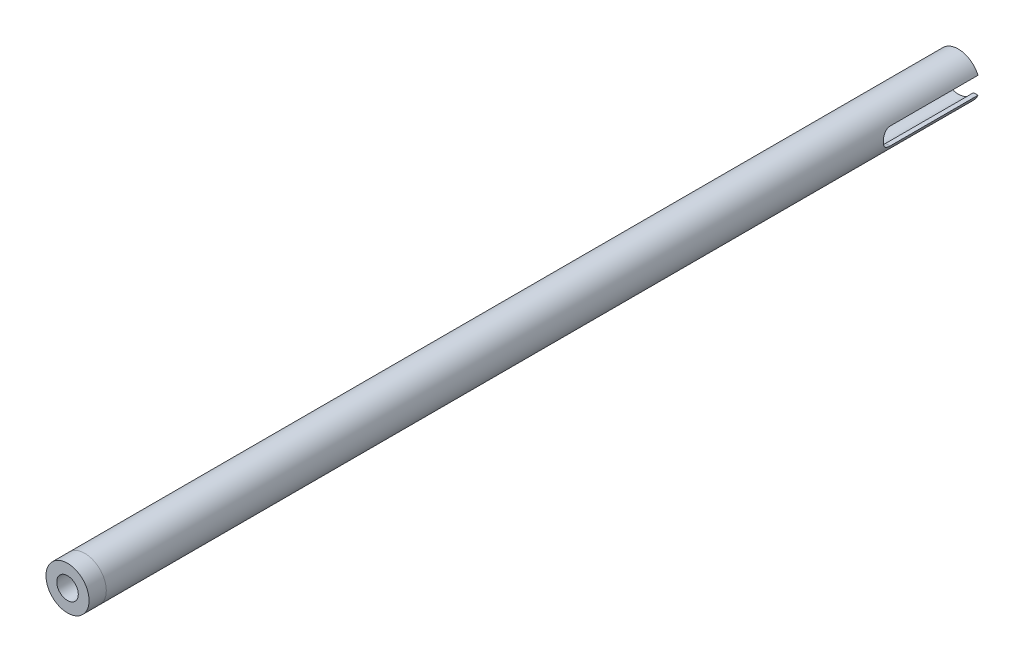
SolidWorks part; units mm, degrees
material "AISI 4130 Steel, annealed at 865C"
ref_plane "Front Plane" through (0, 0, 0) normal (0, 0, 1) x (1, 0, 0)
ref_plane "Top Plane" through (0, 0, 0) normal (0, 1, 0) x (1, 0, 0)
ref_plane "Right Plane" through (0, 0, 0) normal (1, 0, 0) x (0, 0, -1)
sketch "Axis" plane through (0, 0, 0) normal (0, 1, 0) x (1, 0, 0)
  line L0 (0, 0) -> (0, 328.0702) construction
  line L1 (0, 0) -> (0, -28.575) construction
  line L2 (0, 328.0702) -> (-7.9375, 328.0702) construction
  line L4 (0, 356.4735) -> (-26.4371, 261.8721) construction
  dimension "D1" = 28.575
  dimension "D2" = 7.9375
sketch "Sketch1" plane through (0, 0, 0) normal (0, 0, 1) x (1, 0, 0)
  line L0 (-7.9375, 0) -> (7.9375, 0) construction
  line L1 (-7.2748, 3.175) -> (7.2748, 3.175)
  line L2 (-7.2748, -3.175) -> (7.2748, -3.175)
  circle A0 centre (0, 0) radius 7.9375
  circle A1 centre (0, 0) radius 6.4643
  circle A2 centre (0, 0) radius 3.9688
  dimension "D1" = 15.875
  dimension "D3" = 7.9375
  dimension "D2" = 1.4732
  dimension "D4" = 6.35
extrude "Threaded insert 1-1" add sketch "Sketch1" against normal blind 6.35 contours A2 L1 A1 | A1 L1 A0 | A2 L0 A1 L1 | A1 L0 A0 L1 | L0 A1 L2 A0 | L0 A2 L2 A1 | A2 L2 A1 | A1 L2 A0 | L0 A1 L2 A2 | L0 A0 L2 A1 | A0 L0 A1 L1 | A1 L0 A2 L1 region at (4.8156, 1.6537, 0) region at (4.8156, -1.6537, 0) region at (6.9501, 1.6161, 0) region at (6.9501, -1.6161, 0) region at (-4.8156, -1.6537, 0) region at (-4.8156, 1.6537, 0) region at (0, 4.6361, 0) region at (0, -4.6361, 0) region at (0, 6.6174, 0) region at (6.4528, -3.3281, 0) region at (-6.9501, -1.6161, 0) region at (-6.9501, 1.6161, 0)
extrude "Threaded insert 1-2" add sketch "Sketch1<3>" against normal blind 9.525 from surface contours A2 L1 A1 | A2 L0 A1 L1 | L0 A2 L2 A1 | A2 L2 A1 | L0 A1 L2 A2 | A1 L0 A2 L1 region at (4.8156, 1.6537, 0) region at (4.8156, -1.6537, 0) region at (-4.8156, -1.6537, 0) region at (-4.8156, 1.6537, 0) region at (0, 4.6361, 0) region at (0, -4.6361, 0) starting at face at (7.9375, 0, -6.35)
sketch "Sketch1<3>" plane through (0, 0, 0) normal (0, 0, 1) x (1, 0, 0) same geometry as "Sketch1"
extrude "A-arm tube" add sketch "Sketch1<4>" against normal up to vertex (328.0702 mm away) from surface separate body contours A1 L1 A0 | A1 L0 A0 L1 | L0 A1 L2 A0 | A1 L2 A0 | L0 A0 L2 A1 | A0 L0 A1 L1 region at (6.9501, 1.6161, 0) region at (6.9501, -1.6161, 0) region at (0, 6.6174, 0) region at (6.4528, -3.3281, 0) region at (-6.9501, -1.6161, 0) region at (-6.9501, 1.6161, 0) up to point (0, 0, -328.0702) starting at face at (6.4643, 0, -6.35)
sketch "Sketch1<4>" plane through (0, 0, 0) normal (0, 0, 1) x (1, 0, 0) same geometry as "Sketch1"
extrude "Apex slot" cut sketch "Sketch1<5>" along normal blind 35.56 from surface contours A0 L0 A1 L1 | L0 A0 L2 A1 | A1 L0 A0 L1 | L0 A1 L2 A0 region at (6.9501, 1.6161, 0) region at (6.9501, -1.6161, 0) region at (-6.9501, -1.6161, 0) region at (-6.9501, 1.6161, 0) starting at face at (6.4643, 0, -328.0702)
sketch "Sketch1<5>" plane through (0, 0, 0) normal (0, 0, 1) x (1, 0, 0) same geometry as "Sketch1"
fillet "Fillet1" radius 3.175 4 edges at (-6.4528, 3.175, -292.5102) (-6.4528, -3.175, -292.5102) (6.4528, -3.175, -292.5102) (6.4528, 3.175, -292.5102)
equation "\"tube diameter\"= 5 / 8"
equation "\"tube thickness\"= .058"
equation "\"apex thickness\"= .25"
equation "\"tube slot\"= 1.4"
equation "\"D1@Sketch1\"=\"tube diameter\""
equation "\"D2@Sketch1\"=\"tube thickness\""
equation "\"threaded insert hole\"= .3125"
equation "\"D3@Sketch1\"=\"threaded insert hole\""
equation "\"D4@Sketch1\"=\"apex thickness\""
equation "\"D1@Apex slot\" = \"tube slot\""
equation "\"D1@Fillet1\"=\"apex thickness\"/2"
equation "\"D2@Axis\"=\"tube diameter\"/2"
